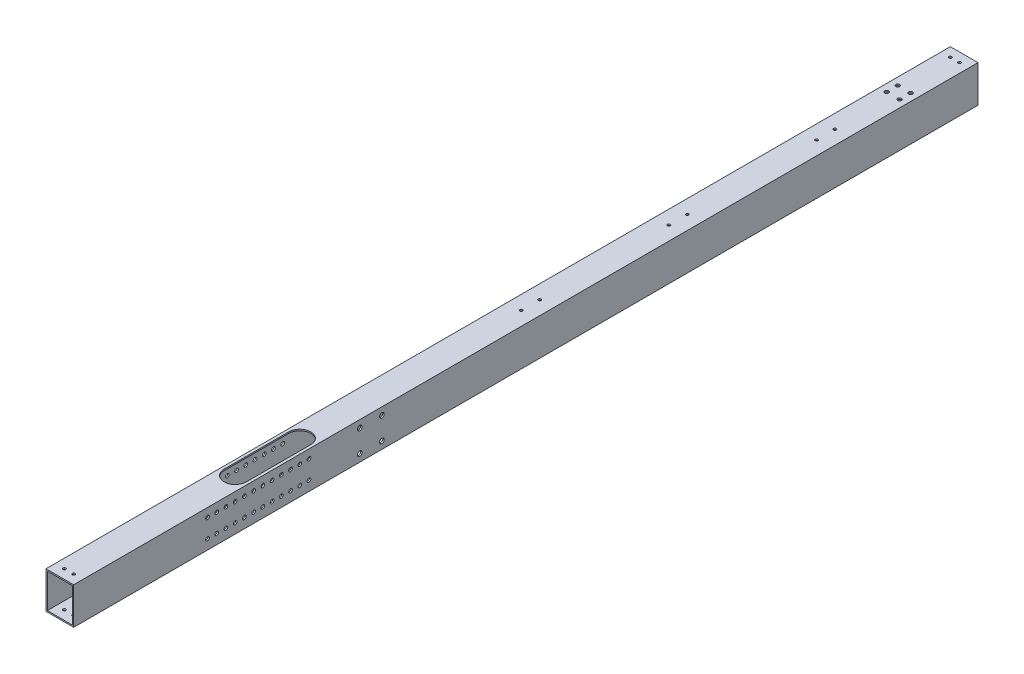
SolidWorks part; units mm, degrees
ref_plane "前视基准面" through (0, 0, 0) normal (0, 0, 1) x (1, 0, 0)
ref_plane "上视基准面" through (0, 0, 0) normal (0, 1, 0) x (1, 0, 0)
ref_plane "右视基准面" through (0, 0, 0) normal (1, 0, 0) x (0, 0, -1)
sketch "草图1" plane through (0, 0, 0) normal (0, 0, 1) x (1, 0, 0)
  line L0 (-13.5, 18.5) -> (13.5, 18.5)
  line L1 (-15, -20) -> (15, -20)
  line L2 (-15, -20) -> (-15, 20)
  line L3 (-15, 20) -> (15, 20)
  line L4 (15, -20) -> (15, 20)
  line L5 (-15, -20) -> (15, 20) construction
  line L6 (-15, 20) -> (15, -20) construction
  line L7 (13.5, -18.5) -> (13.5, 18.5)
  line L8 (-13.5, -18.5) -> (13.5, -18.5)
  line L9 (-13.5, -18.5) -> (-13.5, 18.5)
  point P0 (0, 0)
  dimension "D1" = 40
  dimension "D2" = 30
  dimension "D3" = 1.5
extrude "凸台-拉伸1" add sketch "草图1" along normal blind 980
sketch "草图2" plane through (0, 20, 0) normal (0, -1, 0) x (-1, 0, 0)
  line L0 (0, 0) -> (0, -50000) construction
  circle A0 centre (11, -65) radius 1.5
  circle A1 centre (-11, -65) radius 1.5
  circle A2 centre (11, -515) radius 1.5
  circle A3 centre (-11, -515) radius 1.5
  circle A4 centre (11, -105) radius 1.5
  circle A5 centre (-11, -105) radius 1.5
  dimension "D1" = 3
  dimension "D4" = 3
  dimension "D7" = 3
  dimension "D2" = 22
  dimension "D3" = 65
  dimension "D6" = 450
  dimension "D8" = 40
extrude "切除-拉伸1" [suppressed] cut sketch "草图2" along normal blind 1040
sketch "草图3" plane through (0, 20, 0) normal (0, -1, 0) x (-1, 0, 0)
  line L0 (0, 0) -> (0, -50000) construction
  line L2 (-16.5, -490) -> (49983.5, -490) construction
  line L3 (13.5, 0) -> (13.5, -980) construction
  line L4 (-13.5, 0) -> (-13.5, -980) construction
  line L5 (-15, 0) -> (15, 0) construction
  circle A0 centre (5, -10) radius 1.5
  circle A1 centre (-5, -10) radius 1.5
  circle A2 centre (-5, -970) radius 1.5
  circle A3 centre (5, -970) radius 1.5
  point P13 (13.5, -490)
  point P16 (-13.5, -490)
  dimension "D1" = 3
  dimension "D2" = 10
  dimension "D3" = 10
extrude "切除-拉伸2" cut sketch "草图3" along normal through all
sketch "草图4" plane through (0, 20, 0) normal (0, -1, 0) x (-1, 0, 0)
  line L1 (-8.2701, -787.5) -> (6.7299, -787.5) construction
  line L2 (-8.2701, -787.5) -> (-8.2701, -772.5) construction
  line L3 (-8.2701, -772.5) -> (6.7299, -772.5) construction
  line L4 (6.7299, -787.5) -> (6.7299, -772.5) construction
  line L5 (-8.2701, -787.5) -> (6.7299, -772.5) construction
  line L6 (-8.2701, -772.5) -> (6.7299, -787.5) construction
  line L7 (-0.7701, -780) -> (49999.2299, -780) construction
  line L8 (-0.7701, -840) -> (-0.7701, -50840) construction
  line L9 (15, -980) -> (-15, -980) construction
  circle A0 centre (-8.2701, -772.5) radius 3.25
  circle A1 centre (6.7299, -772.5) radius 3.25
  circle A2 centre (6.7299, -787.5) radius 3.25
  circle A3 centre (-8.2701, -787.5) radius 3.25
  point P0 (-0.7701, -780)
  dimension "D4" = 6.5
  dimension "D1" = 15
  dimension "D2" = 15
  dimension "D3" = 200
extrude "切除-拉伸3" cut sketch "草图4" along normal blind 21
sketch "草图5" plane through (0, 20, 0) normal (0, -1, 0) x (-1, 0, 0)
  line L0 (0, 0) -> (0, -50000) construction
  line L2 (0, -140) -> (0, -300) construction
  line L3 (0, -320) -> (0, -480) construction
  line L4 (15, 0) -> (-15, 0) construction
  circle A0 centre (0, -140) radius 1.5
  circle A1 centre (0, -160) radius 1.5
  circle A2 centre (0, -300) radius 1.5
  circle A3 centre (0, -320) radius 1.5
  circle A4 centre (0, -480) radius 1.5
  circle A5 centre (0, -460) radius 1.5
  dimension "D1" = 3
  dimension "D2" = 3
  dimension "D3" = 20
  dimension "D4" = 140
  dimension "D6" = 160
  dimension "D8" = 160
  dimension "D5" = 2
  dimension "D7" = 2
extrude "切除-拉伸4" cut sketch "草图5" along normal through all
sketch "草图8" plane through (0, -20, 0) normal (0, -1, 0) x (1, 0, 0)
  line L0 (0, 160) -> (0, 140) construction
  line L1 (7.5, 160) -> (7.5, 140)
  line L2 (-7.5, 160) -> (-7.5, 140)
  line L3 (0, 480) -> (0, 460) construction
  line L4 (7.5, 480) -> (7.5, 460)
  line L5 (-7.5, 480) -> (-7.5, 460)
  line L6 (0, 320) -> (0, 300) construction
  line L7 (7.5, 320) -> (7.5, 300)
  line L8 (-7.5, 320) -> (-7.5, 300)
  arc A0 (7.5, 160) -> (-7.5, 160) centre (0, 160) ccw
  arc A1 (-7.5, 140) -> (7.5, 140) centre (0, 140) ccw
  arc A2 (7.5, 480) -> (-7.5, 480) centre (0, 480) ccw
  arc A3 (-7.5, 460) -> (7.5, 460) centre (0, 460) ccw
  arc A4 (7.5, 320) -> (-7.5, 320) centre (0, 320) ccw
  arc A5 (-7.5, 300) -> (7.5, 300) centre (0, 300) ccw
  point P4 (0, 150)
  point P13 (0, 470)
  point P18 (0, 310)
  dimension "D1" = 7.5
  dimension "D2" = 7.5
  dimension "D3" = 7.5
extrude "切除-拉伸6" cut sketch "草图8" against normal blind 10
sketch "草图9" plane through (0, -20, 0) normal (0, -1, 0) x (1, 0, 0)
  line L0 (0, 980) -> (0, -135.6802) construction
  line L1 (-15, 980) -> (15, 980) construction
  circle A4 centre (10, 787.5) radius 1.6
  circle A5 centre (10, 774.5) radius 1.6
  circle A6 centre (-10, 774.5) radius 1.6
  circle A7 centre (-10, 787.5) radius 1.6
  dimension "D1" = 3.2
  dimension "D3" = 192.5
  dimension "D4" = 2
  dimension "D5" = 13
  dimension "D6" = 10
extrude "切除-拉伸7" cut sketch "草图9" against normal blind 10
pattern_linear "阵列(线性)1" count 4 spacing 13 along (0, 0, -1) of "切除-拉伸7"
sketch "草图10" plane through (-15, 0, 0) normal (-1, 0, 0) x (0, 0, 1)
  line L1 (0, 0) -> (664.4549, 0) construction
  line L2 (980, 20) -> (980, -20) construction
  circle A0 centre (646, 12) radius 2.55
  circle A1 centre (670, 12) radius 2.55
  circle A2 centre (646, -12) radius 2.55
  circle A3 centre (670, -12) radius 2.55
  dimension "D1" = 310
  dimension "D2" = 5.1
  dimension "D5" = 24
  dimension "D6" = 12
  dimension "D3" = 2
  dimension "D4" = 2
extrude "切除-拉伸8" cut sketch "草图10" against normal blind 51
sketch "草图11" plane through (-15, 0, 0) normal (-1, 0, 0) x (0, 0, 1)
  line L1 (980, 20) -> (980, -20) construction
  circle A0 centre (725, 10.6252) radius 2
  circle A1 centre (725, -9.3748) radius 2
  circle A2 centre (735, 10.6252) radius 2
  circle A3 centre (735, -9.3748) radius 2
  circle A4 centre (745, 10.6252) radius 2
  circle A5 centre (745, -9.3748) radius 2
  circle A6 centre (755, 10.6252) radius 2
  circle A7 centre (755, -9.3748) radius 2
  circle A8 centre (765, 10.6252) radius 2
  circle A9 centre (765, -9.3748) radius 2
  circle A10 centre (775, 10.6252) radius 2
  circle A11 centre (775, -9.3748) radius 2
  circle A12 centre (785, 10.6252) radius 2
  circle A13 centre (785, -9.3748) radius 2
  circle A14 centre (795, 10.6252) radius 2
  circle A15 centre (795, -9.3748) radius 2
  circle A16 centre (805, 10.6252) radius 2
  circle A17 centre (805, -9.3748) radius 2
  circle A18 centre (815, 10.6252) radius 2
  circle A19 centre (815, -9.3748) radius 2
  circle A20 centre (825, 10.6252) radius 2
  circle A21 centre (825, -9.3748) radius 2
  circle A22 centre (835, 10.6252) radius 2
  circle A23 centre (835, -9.3748) radius 2
  dimension "D1" = 4
  dimension "D2" = 2
  dimension "D4" = 145
  dimension "D3" = 12
extrude "切除-拉伸9" cut sketch "草图11" against normal blind 51
sketch "草图12" plane through (0, 20, 0) normal (0, 1, 0) x (1, 0, 0)
  line L0 (0, 0) -> (0, -98.6612) construction
  line L1 (15, 0) -> (-15, 0) construction
  circle A0 centre (-7, -65) radius 2.1
  circle A1 centre (-7, -77) radius 2.1
  circle A2 centre (7, -77) radius 2.1
  circle A3 centre (7, -65) radius 2.1
  dimension "D1" = 65
  dimension "D2" = 4.2
  dimension "D4" = 14
  dimension "D3" = 2
extrude "切除-拉伸10" cut sketch "草图12" against normal blind 10
sketch "草图13" plane through (0, -20, 0) normal (0, -1, 0) x (1, 0, 0)
  line L0 (0, 70.1408) -> (0, 99.7127) construction
  line L1 (-8.2089, 70.1408) -> (-8.2089, 99.7127)
  line L2 (8.2089, 70.1408) -> (8.2089, 99.7127)
  arc A0 (-8.2089, 70.1408) -> (8.2089, 70.1408) centre (0, 70.1408) ccw
  arc A1 (8.2089, 99.7127) -> (-8.2089, 99.7127) centre (0, 99.7127) ccw
  point P3 (0, 84.9268)
extrude "切除-拉伸11" cut sketch "草图13" against normal blind 10
sketch "草图14" plane through (0, 20, 0) normal (0, 1, 0) x (1, 0, 0)
  line L0 (0, -720) -> (0, -790) construction
  line L1 (12, -720) -> (12, -790)
  line L2 (-12, -720) -> (-12, -790)
  line L3 (15, -980) -> (-15, -980) construction
  arc A0 (12, -720) -> (-12, -720) centre (0, -720) ccw
  arc A1 (-12, -790) -> (12, -790) centre (0, -790) ccw
  point P3 (0, -755)
  dimension "D1" = 12
  dimension "D2" = 70
  dimension "D3" = 225
extrude "切除-拉伸12" cut sketch "草图14" against normal blind 10
equation "\"5。7\"=6"
